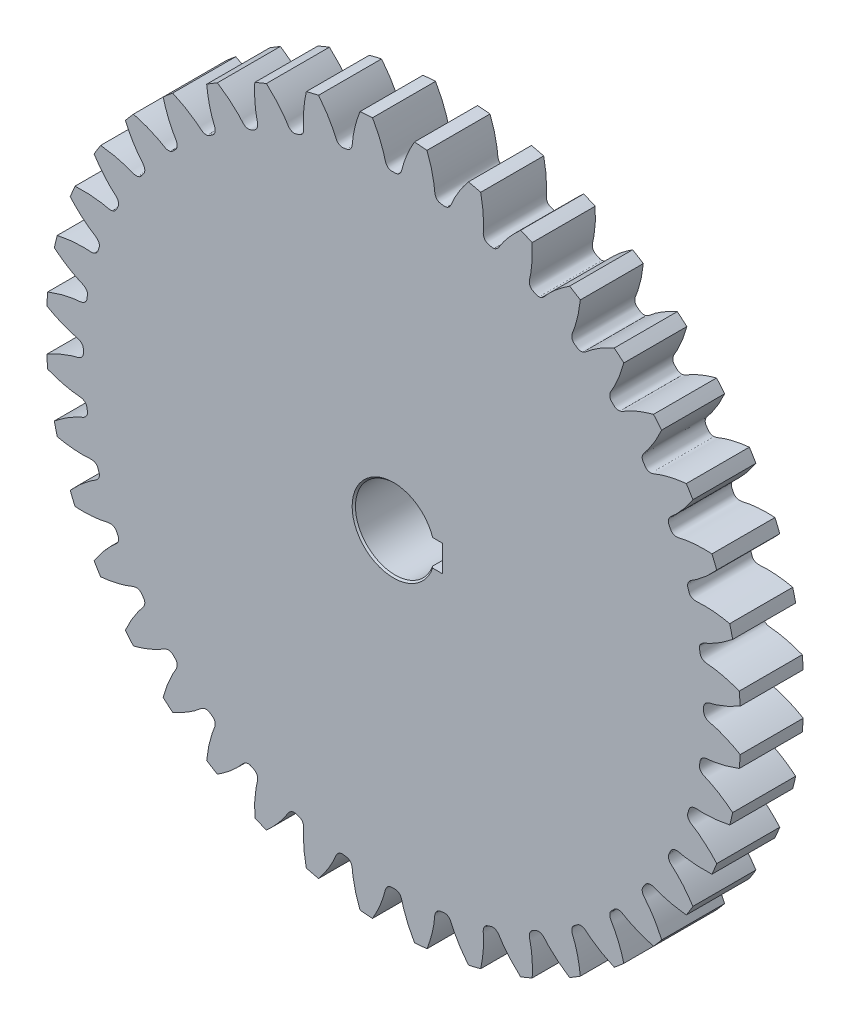
SolidWorks part; units mm, degrees
ref_plane "Front Plane" through (0, 0, 0) normal (0, 0, 1) x (1, 0, 0)
ref_plane "Top Plane" through (0, 0, 0) normal (0, 1, 0) x (1, 0, 0)
ref_plane "Right Plane" through (0, 0, 0) normal (1, 0, 0) x (0, 0, -1)
ref_axis "Axis1" through (0, 0, 55) along (0, 0, -1)
sketch "SketchRevolvebanhrangmamxoayGear" plane through (0, 0, 0) normal (1, 0, 0) x (0, 0, -1)
  line L0 (0, 0) -> (1, 0) construction
  line L1 (-9.525, 0) -> (-9.525, 105)
  line L2 (-9.525, 105) -> (9.525, 105)
  line L3 (9.525, 105) -> (9.525, 0)
  line L4 (9.525, 0) -> (-9.525, 0)
  dimension "Side1" = 9.525
  dimension "OutsideRadius" = 105
  dimension "Side2" = 9.525
revolve "banhrangmamxoayGear" add sketch "SketchRevolvebanhrangmamxoayGear" angle 360 about L0
sketch "SketchToothbanhrangmamxoayGear" plane through (0, 0, 0) normal (0, 0, 1) x (1, 0, 0)
  arc A0 (105.0502, 6.4816) -> (105.0502, -6.4816) centre (0, 0) cw
  spline S0 degree 3 poles (105.0502, -6.4816) (104.5832, -6.2086) (103.8886, -5.8185) (102.9662, -5.3328) (102.3076, -5.0008) (101.67, -4.6934) (101.0538, -4.4097) (100.4598, -4.1489) (99.8885, -3.91) (99.3406, -3.6922) (98.8165, -3.4946) (98.3169, -3.3163) (97.8422, -3.1563) (97.393, -3.0137) (96.9697, -2.8875) (96.5725, -2.777) (96.0204, -2.632) (95.5155, -2.5272) (95.0795, -2.3583) (94.8571, -2.2533) (94.6337, -2.1224) (94.4053, -1.9524) (94.1726, -1.7224) (93.9511, -1.4064) (93.7929, -1.008) (93.7313, -0.523) (93.7605, 0) (93.7313, 0.523) (93.7929, 1.008) (93.9511, 1.4064) (94.1726, 1.7224) (94.4053, 1.9524) (94.6337, 2.1224) (94.8571, 2.2533) (95.0795, 2.3583) (95.5155, 2.5272) (96.0204, 2.632) (96.5725, 2.777) (96.9697, 2.8875) (97.393, 3.0137) (97.8422, 3.1563) (98.3169, 3.3163) (98.8165, 3.4946) (99.3406, 3.6922) (99.8885, 3.91) (100.4598, 4.1489) (101.0538, 4.4097) (101.67, 4.6934) (102.3076, 5.0008) (102.9662, 5.3328) (103.8886, 5.8185) (104.5832, 6.2086) (105.0502, 6.4816) knots 0 0 0 0 0.058973 0.086848 0.113648 0.139373 0.164024 0.1876 0.210102 0.231529 0.251881 0.271159 0.289362 0.30649 0.322544 0.337523 0.351428 0.384797 0.393515 0.40234 0.411585 0.421701 0.433309 0.447108 0.46349 0.479494 0.5 0.520506 0.53651 0.552892 0.566691 0.578299 0.588415 0.59766 0.606485 0.615203 0.648572 0.662477 0.677456 0.69351 0.710638 0.728841 0.748119 0.768471 0.789898 0.8124 0.835976 0.860627 0.886352 0.913152 0.941027 1 1 1 1
extrude "ToothExtrudeCutbanhrangmamxoayGear" cut sketch "SketchToothbanhrangmamxoayGear" against normal blind 9.525 and the other way blind 9.525
pattern_circular "PatternbanhrangmamxoayGear" count 40 every 9 about axis through (0, 0, 55) along (0, 0, -1) of "ToothExtrudeCutbanhrangmamxoayGear"
sketch "HubSketchSide1" plane through (0, 0, 0) normal (1, 0, 0) x (0, 0, -1)
  line L0 (0, 0) -> (1, 0) construction
  line L1 (9.525, 25) -> (29.525, 25)
  line L2 (29.525, 25) -> (29.525, 0)
  line L3 (29.525, 0) -> (9.525, 0)
  line L4 (9.525, 0) -> (9.525, 25)
  dimension "HubRadius1" = 25
  dimension "HubFace1" = 29.525
  dimension "HubComponentFace1" = 9.525
revolve "HubRevolve1" add sketch "HubSketchSide1" angle 360 about L0
sketch "BoreRevolveSketch" plane through (0, 0, 0) normal (1, 0, 0) x (0, 0, -1)
  line L0 (0, 0) -> (1, 0) construction
  line L1 (-9.525, 0) -> (29.525, 0)
  line L2 (29.525, 0) -> (29.525, 12.5)
  line L3 (29.525, 12.5) -> (29.025, 12)
  line L4 (29.025, 12) -> (-9.025, 12)
  line L5 (-9.025, 12) -> (-9.525, 12.5)
  line L6 (-9.525, 12.5) -> (-9.525, 0)
  dimension "BoreSide1" = 29.525
  dimension "TaperSide1" = 12.5
  dimension "Chamfer1X" = 0.5
  dimension "Chamfer1Y" = 0.5
  dimension "BoreSide2" = 9.525
  dimension "TaperSide2" = 12.5
revolve "BoreRevolveCut" cut sketch "BoreRevolveSketch" angle 360 about L0
sketch "KeywaySketch" plane through (0, 0, 0) normal (0, 0, 1) x (1, 0, 0)
  line L0 (0, 0) -> (29.6274, 0) construction
  line L1 (14.8137, 4) -> (7.8137, 4)
  line L2 (7.8137, 4) -> (7.8137, -4)
  line L3 (7.8137, -4) -> (14.8137, -4)
  line L4 (14.8137, -4) -> (14.8137, 4)
  dimension "KeyWidth1" = 4
  dimension "KeyAngle" = 4
  dimension "KeyInside" = 7.8137
  dimension "KeyWidth2" = 4
  dimension "KeyOutside" = 14.8137
extrude "Keyway" cut sketch "KeywaySketch" against normal through all and the other way through all
sketch "AuxiliarySketchbanhrangmamxoayGear" plane through (0, 0, 0) normal (0, 0, 1) x (1, 0, 0)
  circle A0 centre (0, 0) radius 100 construction
  circle A1 centre (0, 0) radius 93.9693 construction
  circle A2 centre (0, 0) radius 95.8342 construction
  circle A3 centre (0, 0) radius 105 construction
  circle A4 centre (0, 0) radius 93.75 construction
  dimension "PitchDiameter" = 200
  dimension "BaseDiameter" = 187.9385
  dimension "FormDiameter" = 191.6683
  dimension "MajorDiameter" = 210
  dimension "MinorDiameter" = 187.5
